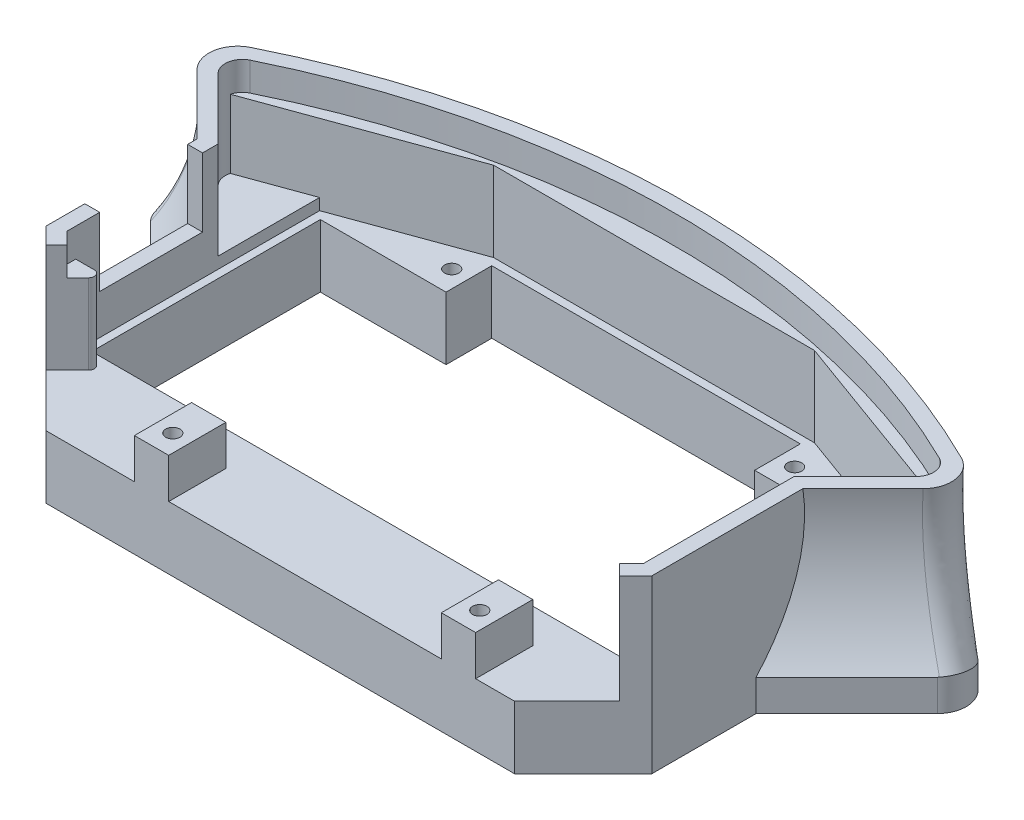
SolidWorks part; units mm, degrees
material "ABS"
ref_plane "Front Plane" through (0, 0, 0) normal (0, 0, 1) x (1, 0, 0)
ref_plane "Top Plane" through (0, 0, 0) normal (0, 1, 0) x (1, 0, 0)
ref_plane "Right Plane" through (0, 0, 0) normal (1, 0, 0) x (0, 0, -1)
sketch "Sketch1" plane through (0, 0, 0) normal (0, 1, 0) x (1, 0, 0)
  line L0 (53, 80) -> (53, 129.1478)
  line L1 (-53, 129.1478) -> (-53, 80)
  line L2 (-41, 68) -> (41, 68)
  line L3 (-53, 80) -> (-41, 68)
  line L4 (41, 68) -> (53, 80)
  circle A0 centre (0, 0) radius 140 construction
  arc A1 (53, 129.1478) -> (-53, 129.1478) centre (0, 0) ccw
  dimension "D1" = 280
  dimension "D3" = 139.6
  dimension "D2" = 106
  dimension "D4" = 68
  dimension "D5" = 80
  dimension "D6" = 135
  dimension "D7" = 135
extrude "Boss-Extrude1" add sketch "Sketch1" along normal blind 30
sketch "Sketch2" plane through (0, 30, 0) normal (0, 1, 0) x (1, 0, 0)
  line L0 (-49, 84) -> (49, 84)
  line L1 (49, 84) -> (49, 124)
  line L2 (49, 124) -> (27, 124)
  line L3 (27, 124) -> (27, 132)
  line L4 (27, 132) -> (-27, 132)
  line L5 (-27, 132) -> (-27, 124)
  line L6 (-27, 124) -> (-49, 124)
  line L7 (-49, 124) -> (-49, 84)
  line L12 (-53, 129.1478) -> (-53, 80) construction
  dimension "D1" = 48
  dimension "D2" = 98
  dimension "D3" = 8
  dimension "D4" = 84
  dimension "D5" = 22
  dimension "D6" = 4
extrude "Cut-Extrude1" cut sketch "Sketch2" against normal up to next
sketch "Sketch3" plane through (0, 30, 0) normal (0, 1, 0) x (1, 0, 0)
  line L0 (-50, 83) -> (50, 83) construction
  line L1 (50, 83) -> (50, 125) construction
  line L2 (50, 125) -> (28, 133) construction
  line L3 (28, 133) -> (-28, 133) construction
  line L4 (-28, 133) -> (-50, 125) construction
  line L5 (-50, 125) -> (-50, 83) construction
  line L7 (-49, 84) -> (-49, 124) construction
  line L8 (-50.4, 125.2802) -> (-50.4, 82.6)
  line L9 (-50.4, 82.6) -> (50.4, 82.6)
  line L10 (50.4, 82.6) -> (50.4, 125.2802)
  line L11 (50.4, 125.2802) -> (28.0705, 133.4)
  line L12 (28.0705, 133.4) -> (-28.0705, 133.4)
  line L13 (-28.0705, 133.4) -> (-50.4, 125.2802)
  line L16 (-49, 84) -> (49, 84) construction
  dimension "D1" = 50
  dimension "D2" = 22
  dimension "D3" = 8
  dimension "D4" = 1
  dimension "D5" = 1
  dimension "D6" = 100
  dimension "D7" = 0.4
extrude "Cut-Extrude2" cut sketch "Sketch3" against normal offset from surface (19 mm away) 11 up to face at (0, 0, -116)
sketch "Sketch5" plane through (0, 30, 0) normal (0, 1, 0) x (1, 0, 0)
  line L1 (-37.48, 68.91) -> (43.8, 68.91) construction
  line L2 (-37.48, 68.91) -> (-37.48, 122.25) construction
  line L3 (-37.48, 122.25) -> (43.8, 122.25) construction
  line L4 (43.8, 68.91) -> (43.8, 122.25) construction
  line L6 (-37.88, 68.51) -> (-37.88, 122.65)
  line L7 (-37.88, 122.65) -> (44.2, 122.65)
  line L8 (44.2, 68.51) -> (44.2, 122.65)
  line L9 (-37.88, 68.51) -> (44.2, 68.51)
  dimension "D1" = 68.91
  dimension "D2" = 43.8
  dimension "D3" = 81.28
  dimension "D4" = 53.34
  dimension "D5" = 0.4
extrude "Cut-Extrude4" cut sketch "Sketch5" against normal offset from surface (12 mm away) 18 up to face at (0, 0, -116)
sketch "Sketch4" plane through (0, 18, 0) normal (0, 1, 0) x (1, 0, 0)
  circle A0 centre (31.18, 71.72) radius 1.25
  circle A1 centre (-22.53, 71.72) radius 1.25
  dimension "D2" = 2.5
  dimension "D1" = 22.53
  dimension "D3" = 8.28
  dimension "D4" = 53.71
extrude "Cut-Extrude3" cut sketch "Sketch4" against normal up to next
sketch "Sketch6" plane through (0, 30, 0) normal (0, 1, 0) x (1, 0, 0)
  line L20 (50.4, 81.077) -> (50.4, 127.3925)
  line L21 (39.923, 70.6) -> (50.4, 81.077)
  line L22 (-39.923, 70.6) -> (39.923, 70.6)
  line L23 (-50.4, 81.077) -> (-39.923, 70.6)
  line L24 (-50.4, 127.3925) -> (-50.4, 81.077)
  line L25 (50.4, 81.077) -> (50.4, 127.3925)
  line L26 (39.923, 70.6) -> (50.4, 81.077)
  line L27 (-39.923, 70.6) -> (39.923, 70.6)
  line L28 (-50.4, 81.077) -> (-39.923, 70.6)
  line L29 (-50.4, 127.3925) -> (-50.4, 81.077)
  arc A7 (50.4, 127.3925) -> (-50.4, 127.3925) centre (0, 0) ccw
  arc A8 (50.4, 127.3925) -> (-50.4, 127.3925) centre (0, 0) ccw
  dimension "D1" = 2.6
extrude "Cut-Extrude5" cut sketch "Sketch6" against normal blind 5
sketch "Sketch7" plane through (0, 0, 0) normal (0, -1, 0) x (1, 0, 0)
  line L0 (73.4563, -118.7111) -> (53, -98.2548)
  line L1 (53, -80) -> (53, -129.1478) construction
  line L2 (53, -98.2548) -> (53, -129.1478)
  line L3 (0, 0) -> (103.3995, -103.3995) construction
  arc A0 (53, -129.1478) -> (73.4563, -118.7111) centre (0, 0) ccw
  arc A1 (-53, -129.1478) -> (53, -129.1478) centre (0, 0) ccw construction
  dimension "D1" = 45
  dimension "D2" = 32
extrude "Boss-Extrude2" add sketch "Sketch7" against normal up to surface (30 mm away) up to face at (0.8892, 30, -88.4744)
ref_plane "Plane1" through (96.0837, 0, -96.0837) normal (-0.7071, 0, 0.7071) x (0, -1, 0)
sketch "Sketch8" plane through (96.0837, 0, -96.0837) normal (-0.7071, 0, 0.7071) x (0, -1, 0)
  line L0 (-30, -32) -> (0, -32) construction
  circle A0 centre (-26, 0) radius 38
  dimension "D3" = 76
  dimension "D1" = 32
  dimension "D2" = 26
extrude "Cut-Extrude6" cut sketch "Sketch8" along normal up to surface (98.9296 mm away) up to face at (53, 18.75, -84.5637)
mirror "Mirror1" about plane through (0, 0, 0) normal (1, 0, 0) of "Boss-Extrude2"
ref_plane "Plane2" through (-96.0837, 0, -96.0837) normal (0.7071, 0, 0.7071) x (0, -1, 0)
sketch "Sketch9" plane through (-96.0837, 0, -96.0837) normal (0.7071, 0, 0.7071) x (0, -1, 0)
  line L0 (-30, 32) -> (0, 32) construction
  circle A0 centre (-26, 0) radius 38
  dimension "D1" = 76
  dimension "D2" = 32
  dimension "D3" = 26
extrude "Cut-Extrude7" cut sketch "Sketch9" along normal up to surface (22.9296 mm away) up to face at (-53, 18.75, -93.6911)
fillet "Fillet2" radius 5 4 edges at (69.0949, 16.9868, -121.3015) (73.4563, 2.753, -118.7111) (-73.4563, 2.753, -118.7111) (-68.9598, 17.6248, -121.3784)
sketch "Sketch11" plane through (0, 11, 0) normal (0, 1, 0) x (1, 0, 0)
  line L0 (-49, 124) -> (-27, 124) construction
  circle A0 centre (-30, 128) radius 1.25
  circle A1 centre (30, 128) radius 1.25
  dimension "D2" = 2.5
  dimension "D1" = 4
  dimension "D3" = 60
  dimension "D4" = 30
extrude "Cut-Extrude9" cut sketch "Sketch11" against normal up to next
sketch "Sketch12" plane through (0, 30, 0) normal (0, 1, 0) x (1, 0, 0)
  line L0 (-61.0884, 118.2069) -> (-50.4, 107.5185)
  line L1 (-50.4, 127.3925) -> (-50.4, 81.077) construction
  line L2 (-50.4, 107.5185) -> (-50.4, 127.3925)
  line L3 (-63.5251, 116.9667) -> (-53, 106.4416) construction
  arc A0 (-50.4, 127.3925) -> (-60.2872, 123.0221) centre (0, 0) ccw
  arc A1 (-60.2872, 123.0221) -> (-61.0884, 118.2069) centre (-58.9671, 120.3282) ccw
  arc A3 (62.1871, 124.9837) -> (-62.1871, 124.9837) centre (0, 0) ccw construction
  dimension "D1" = 2.6
  dimension "D2" = 3
extrude "Cut-Extrude10" cut sketch "Sketch12" against normal offset from surface (17 mm away) 5 up to face at (-22.53, 18, -70.47) offset beyond the face yes
sketch "Sketch14" plane through (0, 13, 0) normal (0, 1, 0) x (1, 0, 0)
  line L0 (-50.4, 127.3925) -> (-61.8629, 123.2241)
  line L1 (-61.8629, 123.2241) -> (-61.8629, 121.1118)
  line L2 (-61.8629, 121.1118) -> (-50.4, 125.2802)
  line L3 (-50.4, 125.2802) -> (-50.4, 127.3925)
  line L4 (-50.4, 125.2802) -> (-28.0705, 133.4) construction
  arc A0 (-60.2872, 123.0221) -> (-61.0884, 118.2069) centre (-58.9671, 120.3282) ccw construction
extrude "Boss-Extrude3" add sketch "Sketch14" along normal up to surface (12 mm away) up to face at (0, 25, -130.2921)
mirror "Mirror2" about plane through (0, 0, 0) normal (1, 0, 0) of "Boss-Extrude3", "Cut-Extrude10"
sketch "Sketch15" plane through (0, 30, 0) normal (0, 1, 0) x (1, 0, 0)
  line L0 (-50.1716, 77.1716) -> (-43.3431, 84)
  line L1 (-53, 80) -> (-41, 68) construction
  line L2 (49, 84) -> (-49, 84) construction
  line L3 (-43.3431, 84) -> (43.3431, 84)
  line L4 (43.3431, 84) -> (50.1716, 77.1716)
  line L5 (41, 68) -> (41.51, 68.51) construction
  line L6 (50.1716, 77.1716) -> (41, 68)
  line L7 (41, 68) -> (-41, 68)
  line L8 (-41, 68) -> (-50.1716, 77.1716)
  dimension "D1" = 4
  dimension "D2" = 4
extrude "Cut-Extrude12" cut sketch "Sketch15" against normal up to surface (12 mm away) up to face at (-22.53, 18, -70.47)
sketch "Sketch16" plane through (0, 18, 0) normal (0, 1, 0) x (1, 0, 0)
  line L0 (-50.1716, 77.1716) -> (-44.7431, 82.6)
  line L1 (-44.7431, 82.6) -> (-25.53, 82.6)
  line L2 (50.4, 82.6) -> (-50.4, 82.6) construction
  line L3 (-25.53, 82.6) -> (-25.53, 68)
  line L4 (41, 68) -> (-41, 68) construction
  line L5 (-25.53, 68) -> (-41, 68)
  line L6 (-41, 68) -> (-50.1716, 77.1716) construction
  line L7 (-41, 68) -> (-50.1716, 77.1716)
  line L8 (44.7431, 82.6) -> (-44.7431, 82.6) construction
  line L9 (-19.53, 68) -> (28.18, 68)
  line L10 (-19.53, 68) -> (-19.53, 82.6)
  line L11 (-19.53, 82.6) -> (28.18, 82.6)
  line L12 (28.18, 68) -> (28.18, 82.6)
  line L13 (34.18, 82.6) -> (34.18, 68)
  line L14 (34.18, 68) -> (41, 68)
  line L15 (41, 68) -> (50.1716, 77.1716)
  line L16 (50.1716, 77.1716) -> (44.7431, 82.6)
  line L17 (44.7431, 82.6) -> (34.18, 82.6)
  circle A0 centre (31.18, 71.72) radius 1.25 construction
  circle A3 centre (-22.53, 71.72) radius 1.25 construction
  dimension "D1" = 3
  dimension "D2" = 3
  dimension "D3" = 3
  dimension "D4" = 3
extrude "Cut-Extrude13" cut sketch "Sketch16" against normal up to surface (7 mm away) up to face at (30, 11, -126.75)
sketch "Sketch17" plane through (0, 0, 0) normal (0, -1, 0) x (1, 0, 0)
  circle A0 centre (-55, -115) radius 1.25
  circle A1 centre (55, -115) radius 1.25
  dimension "D1" = 2.5
  dimension "D2" = 115
  dimension "D3" = 55
  dimension "D4" = 55
extrude "Cut-Extrude14" cut sketch "Sketch17" against normal blind 12
fillet "Fillet3" radius 1 2 edges at (44.7431, 18, -82.6) (-44.7431, 18, -82.6)
sketch "Sketch18" plane through (0, 18, 0) normal (0, 1, 0) x (1, 0, 0)
  line L0 (34.18, 82.6) -> (34.18, 68) construction
  line L1 (-25.53, 82.6) -> (34.18, 82.6)
  line L2 (-25.53, 82.6) -> (-25.53, 78)
  line L3 (-25.53, 78) -> (34.18, 78)
  line L4 (34.18, 82.6) -> (34.18, 78)
  line L5 (-19.53, 68) -> (-25.53, 68) construction
  dimension "D1" = 10
extrude "Cut-Extrude15" cut sketch "Sketch18" against normal up to surface (7 mm away) up to face at (30, 11, -126.75)
sketch "Sketch19" plane through (0, 30, 0) normal (0, 1, 0) x (1, 0, 0)
  line L0 (-53, 106.7401) -> (-53, 98.2548) construction
  line L1 (-53, 104.7916) -> (-49, 104.7916)
  line L2 (-53, 104.7916) -> (-53, 86.7916)
  line L3 (-53, 86.7916) -> (-49, 86.7916)
  line L4 (-49, 104.7916) -> (-49, 86.7916)
  line L6 (-49, 84) -> (-49, 124) construction
  circle A0 centre (-22.53, 71.72) radius 1.25 construction
  dimension "D1" = 15.0716
  dimension "D2" = 18
extrude "Cut-Extrude16" cut sketch "Sketch19" against normal up to surface (12 mm away) up to face at (-22.53, 18, -73)
